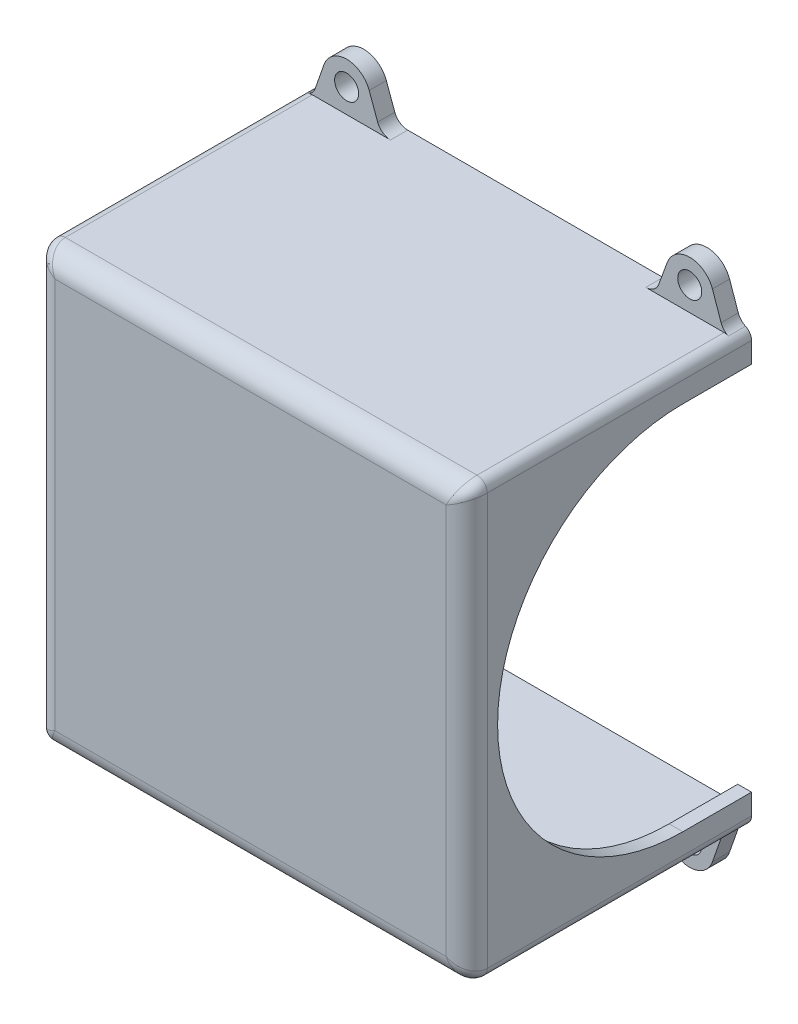
SolidWorks part; units mm, degrees
ref_plane "Front" through (0, 0, 0) normal (0, 0, 1) x (1, 0, 0)
ref_plane "Top" through (0, 0, 0) normal (0, 1, 0) x (1, 0, 0)
ref_plane "Right" through (0, 0, 0) normal (1, 0, 0) x (0, 0, -1)
sketch "Эскиз1" plane through (0, 0, 0) normal (0, 0, 1) x (1, 0, 0)
  line L1 (-31.5, 31.5) -> (31.5, 31.5)
  line L2 (-31.5, 31.5) -> (-31.5, -31.5)
  line L3 (-31.5, -31.5) -> (31.5, -31.5)
  line L4 (31.5, 31.5) -> (31.5, -31.5)
  point P4 (0, 31.5)
  point P5 (31.5, 0)
  dimension "D1" = 63
  dimension "D2" = 63
extrude "Основа" add sketch "Эскиз1" along normal blind 41.5
fillet "Скругление1" radius 3 4 edges at (0, 31.5, 41.5) (31.5, 0, 41.5) (0, -31.5, 41.5) (-31.5, 0, 41.5)
shell "Оболочка1" thickness 2 removed face at (0, 0, 0)
sketch "Эскиз2" plane through (0, 0, 0) normal (0, 0, -1) x (-1, 0, 0)
  line L0 (-28.5, 45) -> (-28.5, 31.5)
  line L1 (-31.5, 31.5) -> (31.5, 31.5) construction
  line L2 (-28.5, 31.5) -> (-21.5, 31.5)
  line L3 (-21.5, 31.5) -> (-21.5, 45)
  line L4 (0, 31.5) -> (0, 0) construction
  line L5 (0, 0) -> (31.5, 0) construction
  line L6 (31.5, 31.5) -> (31.5, -31.5) construction
  line L7 (21.5, 31.5) -> (21.5, 45)
  line L8 (28.5, 31.5) -> (21.5, 31.5)
  line L9 (28.5, 45) -> (28.5, 31.5)
  line L10 (28.5, -45) -> (28.5, -31.5)
  line L11 (28.5, -31.5) -> (21.5, -31.5)
  line L12 (21.5, -31.5) -> (21.5, -45)
  line L13 (-21.5, -31.5) -> (-21.5, -45)
  line L14 (-28.5, -31.5) -> (-21.5, -31.5)
  line L15 (-28.5, -45) -> (-28.5, -31.5)
  circle A0 centre (-25, 45) radius 1.75
  arc A1 (-21.5, 45) -> (-28.5, 45) centre (-25, 45) ccw
  arc A2 (21.5, 45) -> (28.5, 45) centre (25, 45) cw
  circle A3 centre (25, 45) radius 1.75
  circle A4 centre (25, -45) radius 1.75
  arc A5 (21.5, -45) -> (28.5, -45) centre (25, -45) ccw
  arc A6 (-21.5, -45) -> (-28.5, -45) centre (-25, -45) cw
  circle A7 centre (-25, -45) radius 1.75
  dimension "D1" = 3.5
  dimension "D2" = 3.5
  dimension "D4" = 90
  dimension "D3" = 50
extrude "Крепеные уши" [suppressed] add sketch "Эскиз2" against normal blind 3
sketch "Эскиз4" [suppressed] plane through (-31.5, 0, 0) normal (1, 0, 0) x (0, 0, -1)
  line L0 (0, -31.5) -> (0, 31.5) construction
  line L1 (0, -29.5) -> (-20, -29.5)
  line L2 (0, -29.5) -> (0, -18.5)
  line L3 (0, -18.5) -> (-20, -18.5)
  line L4 (-20, -29.5) -> (-20, -18.5)
  line L5 (0, 31.5) -> (0, -31.5) construction
  line L6 (0, 29.5) -> (-20, 29.5)
  line L7 (0, 29.5) -> (0, 7.5)
  line L8 (0, 7.5) -> (-20, 7.5)
  line L9 (-20, 29.5) -> (-20, 7.5)
  line L11 (-42, -29.5) -> (0, -29.5) construction
  line L12 (-42, 29.5) -> (0, 29.5) construction
  dimension "D1" = 22
  dimension "D2" = 20
  dimension "D3" = 20
  dimension "D4" = 11
extrude "Под провода со стороны i2c" [suppressed] cut sketch "Эскиз4" along normal up to next
sketch "Эскиз5" [suppressed] plane through (31.5, 0, 0) normal (1, 0, 0) x (0, 0, -1)
  line L3 (-20, -29.5) -> (0, -29.5)
  line L5 (-20, 29.5) -> (0, 29.5)
  line L6 (-20, 29.5) -> (-20, -29.5)
  line L10 (0, 29.5) -> (0, -29.5)
  line L11 (-42, -29.5) -> (0, -29.5) construction
  dimension "D4" = 20
extrude "Под провода со стороны pwm входов" [suppressed] cut sketch "Эскиз5" against normal up to next
sketch "Эскиз7" plane through (0, -31.5, 0) normal (0, -1, 0) x (1, 0, 0)
  line L1 (-20, 4) -> (20, 4)
  line L2 (-20, 4) -> (-20, 0)
  line L3 (-20, 0) -> (20, 0)
  line L4 (20, 4) -> (20, 0)
  point P4 (0, 0)
  dimension "D1" = 4
  dimension "D2" = 40
extrude "Под уши посдтавки" [suppressed] cut sketch "Эскиз7" against normal through all and the other way through all
fillet "Скругление2" [suppressed] radius 5
fillet "Скругление3" [suppressed] radius 1
fillet "Скругление5" [suppressed] radius 2
sketch "Эскиз6" plane through (-31.5, 0, 0) normal (-1, 0, 0) x (0, 0, 1)
  line L5 (10, -27) -> (0, -27)
  line L6 (0, -27) -> (0, 27)
  line L7 (0, 27) -> (10, 27)
  line L8 (0, 31.5) -> (0, -31.5) construction
  arc A0 (10, -27) -> (10, 27) centre (10, 0) ccw
  point P8 (0, 0)
  dimension "D1" = 10
  dimension "D2" = 54
extrude "Арочный вырез" cut sketch "Эскиз6" against normal up to next
mirror "Зеркальное отражение1" about plane through (0, 0, 0) normal (1, 0, 0) of "Арочный вырез"
fillet "Скругление6" [suppressed] radius 1
sketch "Эскиз8" plane through (0, 0, 0) normal (0, 0, -1) x (-1, 0, 0)
  line L0 (0, 0) -> (0, 31.5) construction
  line L2 (0, 0) -> (31.5, 0) construction
  line L3 (31.5, -27) -> (31.5, 27) construction
  line L4 (-28.3044, 36.1536) -> (-29.929, 31.5)
  line L7 (-21.7114, 36.198) -> (-20, 31.5)
  line L10 (-29.929, 31.5) -> (-20, 31.5)
  line L11 (29.929, 31.5) -> (20, 31.5)
  line L13 (21.7114, 36.198) -> (20, 31.5)
  line L14 (28.3044, 36.1536) -> (29.929, 31.5)
  line L15 (28.3044, -36.1536) -> (29.929, -31.5)
  line L16 (21.7114, -36.198) -> (20, -31.5)
  line L18 (29.929, -31.5) -> (20, -31.5)
  line L19 (-29.929, -31.5) -> (-20, -31.5)
  line L21 (-21.7114, -36.198) -> (-20, -31.5)
  line L22 (-28.3044, -36.1536) -> (-29.929, -31.5)
  circle A0 centre (-25, 35) radius 1.75
  arc A1 (-21.7114, 36.198) -> (-28.3044, 36.1536) centre (-25, 35) ccw
  arc A2 (21.7114, 36.198) -> (28.3044, 36.1536) centre (25, 35) cw
  circle A3 centre (25, 35) radius 1.75
  circle A4 centre (25, -35) radius 1.75
  arc A5 (21.7114, -36.198) -> (28.3044, -36.1536) centre (25, -35) ccw
  arc A6 (-21.7114, -36.198) -> (-28.3044, -36.1536) centre (-25, -35) cw
  circle A7 centre (-25, -35) radius 1.75
  circle A8 centre (-25, 35) radius 3.5 construction
  dimension "D1" = 3.5
  dimension "D2" = 7
  dimension "D4" = 7
  dimension "D3" = 70
  dimension "D5" = 50
extrude "Крепеные уши поуже" add sketch "Эскиз8" against normal blind 2.5
fillet "Скругление4" radius 1.5 8 edges at (-30.6213, -30.6213, 40.6213) (-30.6213, 30.6213, 40.6213) (30.6213, 30.6213, 40.6213) (30.6213, -30.6213, 40.6213) (-31.5, -31.5, 19.25) (-31.5, 31.5, 19.25) (31.5, 31.5, 19.25) (31.5, -31.5, 19.25)
fillet "Скругление8" [suppressed] radius 2
fillet "Скругление9" radius 2 8 edges at (-29.929, 31.5, 1.25) (-20, 31.5, 1.25) (29.929, 31.5, 1.25) (20, 31.5, 1.25) (29.929, -31.5, 1.25) (20, -31.5, 1.25) (-20, -31.5, 1.25) (-29.929, -31.5, 1.25)
